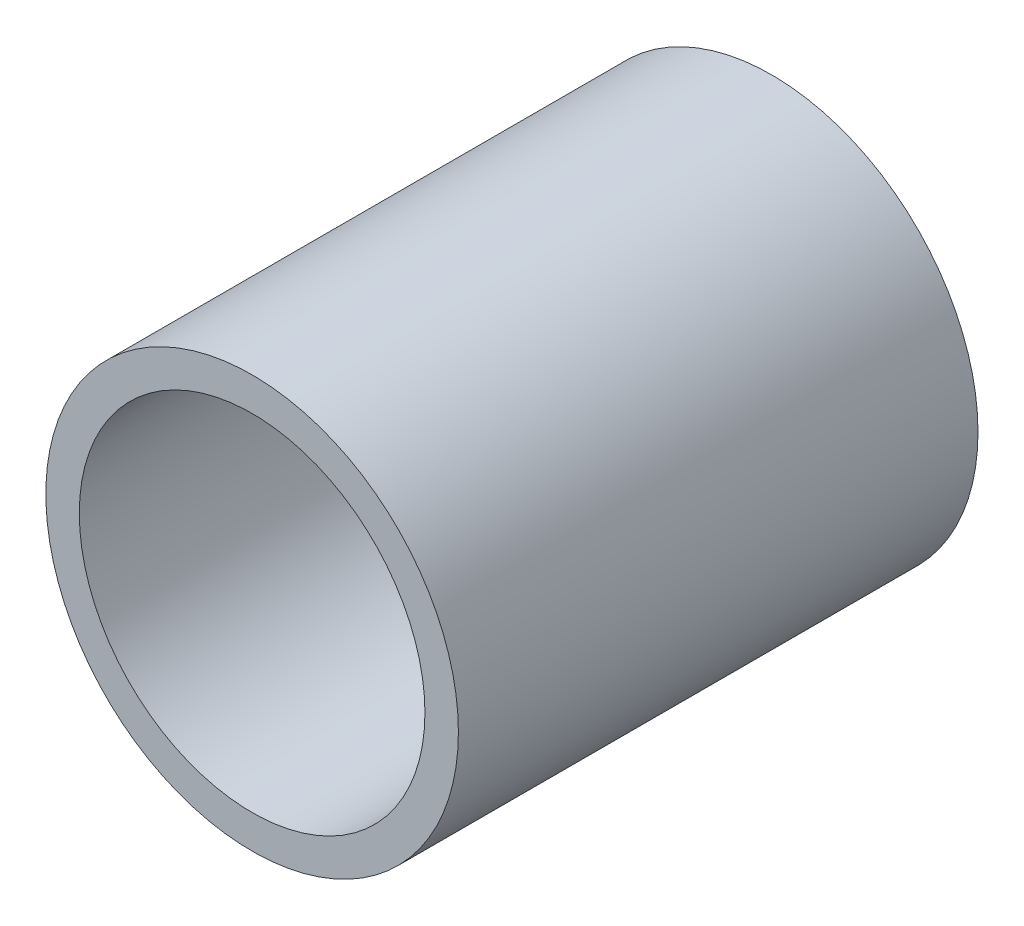
SolidWorks part; units mm, degrees
ref_plane "Front Plane" through (0, 0, 0) normal (0, 0, 1) x (1, 0, 0)
ref_plane "Top Plane" through (0, 0, 0) normal (0, 1, 0) x (1, 0, 0)
ref_plane "Right Plane" through (0, 0, 0) normal (1, 0, 0) x (0, 0, -1)
sketch "Sketch1" plane through (0, 0, 0) normal (0, 0, 1) x (1, 0, 0)
  circle A0 centre (-0.752, 0) radius 18.5
  circle A2 centre (-0.752, 0) radius 15.5
extrude "Boss-Extrude1" add sketch "Sketch1" along normal blind 46.6
sketch "Sketch2" plane through (0, 0, 0) normal (0, 0, -1) x (-1, 0, 0)
